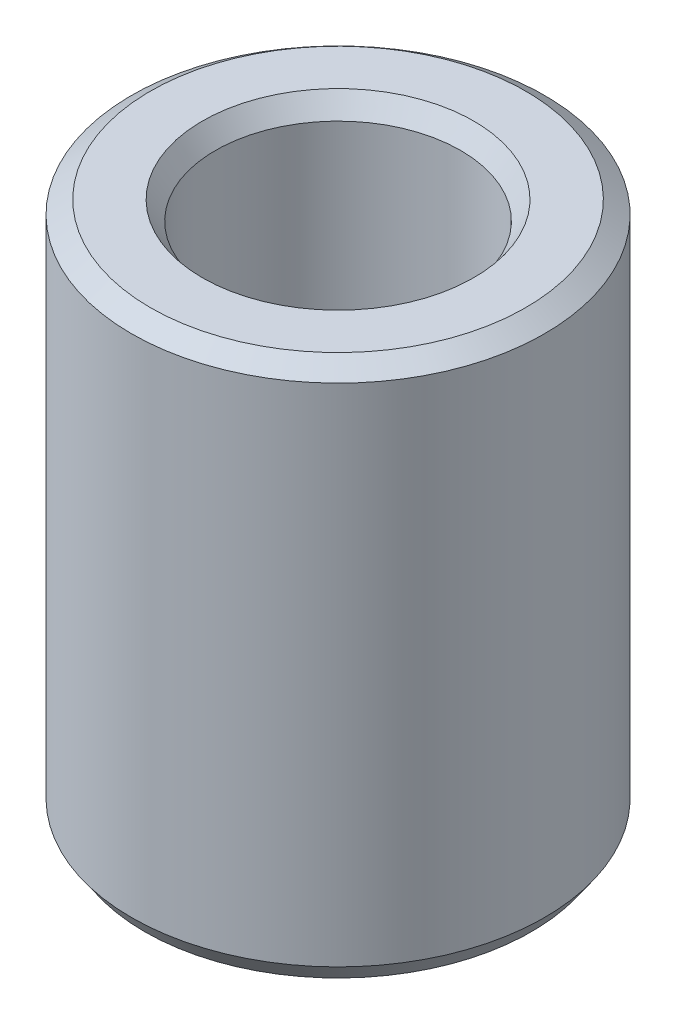
SolidWorks part; units mm, degrees
ref_plane "Front Plane" through (0, 0, 0) normal (0, 0, 1) x (1, 0, 0)
ref_plane "Top Plane" through (0, 0, 0) normal (0, 1, 0) x (1, 0, 0)
ref_plane "Right Plane" through (0, 0, 0) normal (1, 0, 0) x (0, 0, -1)
sketch "Sketch1" plane through (0, 0, 0) normal (0, 1, 0) x (1, 0, 0)
  circle A0 centre (0, 0) radius 55
  dimension "SLEEVE_OD" = 110
extrude "Boss-Extrude1" add sketch "Sketch1" along normal blind 143.1776
sketch "Sketch2" plane through (0, 0, 0) normal (0, 1, 0) x (1, 0, 0)
  circle A0 centre (0, 0) radius 32.6556
  dimension "BORE_D" = 65.3112
extrude "Cut-Extrude1" cut sketch "Sketch2" along normal through all
chamfer "Chamfer1" distance 3.4965 angle 55.204 4 edges at (0, 143.1776, 32.6556) (0, 0, 32.6556) (0, 0, 55) (0, 143.1776, 55) first distance on face at (0, 143.1776, 32.6556) first distance on face at (0, 0, 32.6556) first distance on face at (0, 143.1776, 55)
